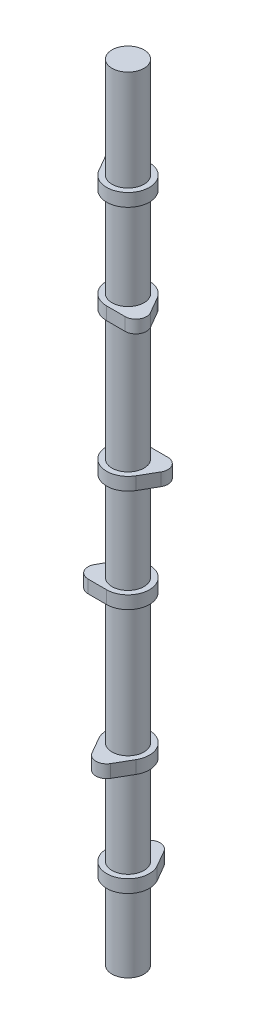
SolidWorks part; units mm, degrees
ref_plane "Front Plane" through (0, 0, 0) normal (0, 0, 1) x (1, 0, 0)
ref_plane "Top Plane" through (0, 0, 0) normal (0, 1, 0) x (1, 0, 0)
ref_plane "Right Plane" through (0, 0, 0) normal (1, 0, 0) x (0, 0, -1)
sketch "Sketch2" plane through (0, 0, 0) normal (0, 1, 0) x (1, 0, 0)
  line L0 (-10.9985, 6.35) -> (-5.4993, 15.875)
  line L1 (10.9985, 6.35) -> (5.4993, 15.875)
  arc A0 (-10.9985, 6.35) -> (10.9985, 6.35) centre (0, 0) ccw
  arc A1 (5.4993, 15.875) -> (-5.4993, 15.875) centre (0, 12.7) ccw
  dimension "D1" = 25.4
  dimension "D2" = 12.7
extrude "Boss-Extrude1" add sketch "Sketch2" along normal mid plane 7.62
ref_axis "Axis1" through (0, 156.7063, 0) along (0, -1, 0)
move or copy body "Body-Move/Copy1" bodies to move or copy 101 copy yes number of copies 1 translate (0, 60.96, 0)
move or copy body "Body-Move/Copy2" bodies to move or copy 102 copy no rotation origin (0, 0, 0) rotation axis (0, 1, 0) rotation angle 180
sketch "Sketch3" plane through (0, 3.81, 0) normal (0, 1, 0) x (1, 0, 0)
  circle A0 centre (0, 0) radius 9.5
  dimension "D1" = 19
extrude "Boss-Extrude2" add sketch "Sketch3" along normal blind 146.05 from offset 25.4 offset against normal yes
pattern_linear "LPattern1" count 3 spacing 146.05 along (0, 1, 0) of bodies 104
move or copy body "Body-Move/Copy3" bodies to move or copy 105 copy no rotation origin (0, 0, 0) rotation axis (0, 1, 0) rotation angle 120
move or copy body "Body-Move/Copy4" bodies to move or copy 106 copy no rotation origin (0, 0, 0) rotation axis (0, -1, 0) rotation angle 120
sketch "Sketch4" plane through (0, -21.59, 0) normal (0, -1, 0) x (1, 0, 0)
  circle A1 centre (0, 0) radius 9.5
  circle A2 centre (0, 0) radius 9.5
  dimension "D1" = 0
extrude "Boss-Extrude3" add sketch "Sketch4" along normal blind 27.94
combine bodies "Combine1" operation type add bodies to combine 109 107 108
